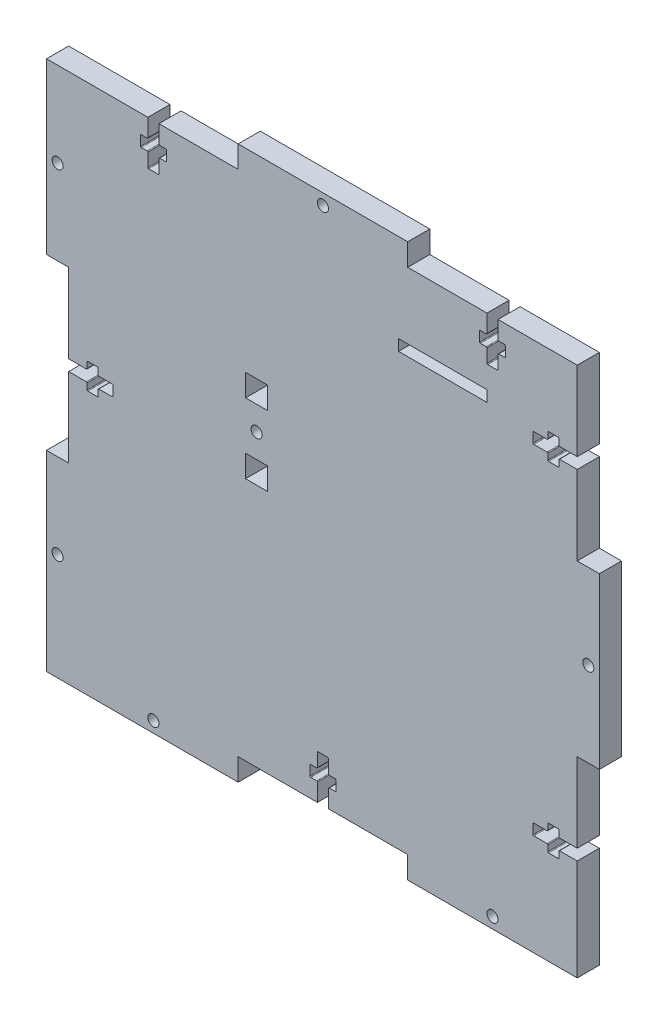
SolidWorks part; units mm, degrees
ref_plane "Front Plane" through (0, 0, 0) normal (0, 0, 1) x (1, 0, 0)
ref_plane "Top Plane" through (0, 0, 0) normal (0, 1, 0) x (1, 0, 0)
ref_plane "Right Plane" through (0, 0, 0) normal (1, 0, 0) x (0, 0, -1)
sketch "Sketch1" plane through (0, 0, 0) normal (0, 0, 1) x (1, 0, 0)
  line L0 (-69, 69) -> (-23, 69)
  line L5 (-75, -75) -> (75, -75) construction
  line L6 (-75, -75) -> (-75, 75) construction
  line L7 (-75, 75) -> (75, 75) construction
  line L8 (75, -75) -> (75, 75) construction
  line L9 (75, 23) -> (69, 23)
  line L10 (69, -23) -> (75, -23)
  line L11 (-69, -69) -> (69, -69) construction
  line L12 (-69, -69) -> (-69, 69) construction
  line L13 (-69, 69) -> (69, 69) construction
  line L14 (69, -69) -> (69, 69) construction
  line L15 (-69, -69) -> (69, 69) construction
  line L16 (69, -69) -> (69, -23)
  line L17 (-23, 69) -> (-23, 75)
  line L18 (-23, 75) -> (23, 75)
  line L19 (23, 75) -> (23, 69)
  line L20 (23, 69) -> (69, 69)
  line L21 (75, -23) -> (75, 23)
  line L22 (69, 23) -> (69, 69)
  line L23 (-75, 23) -> (-69, 23)
  line L24 (-69, 69) -> (-75, 69)
  line L25 (-75, 69) -> (-75, 23)
  line L26 (69, -69) -> (69, -75)
  line L27 (69, -75) -> (23, -75)
  line L28 (23, -75) -> (23, -69)
  line L29 (23, -69) -> (-23, -69)
  line L30 (-23, -69) -> (-23, -75)
  line L31 (-23, -75) -> (-69, -75)
  line L32 (-69, -75) -> (-69, -69) construction
  line L33 (-69, 23) -> (-69, -23)
  line L34 (-69, -23) -> (-75, -23)
  line L35 (-75, -23) -> (-75, -69)
  line L36 (-75, -69) -> (-69, -69) construction
  line L37 (-46, 69) -> (-46, -75) construction
  line L38 (-69, 69) -> (69, -69) construction
  line L39 (-75, -75) -> (-69, -75)
  line L40 (-75, -75) -> (-75, -69)
  point P0 (0, 0)
  point P6 (-7, -7)
  point P26 (0, -75)
  point P27 (-75, 0)
  dimension "D1" = 150
  dimension "D2" = 150
  dimension "D5" = 46
  dimension "D3" = 6
  dimension "D6" = 6
  dimension "D7" = 6
extrude "Box Side" add sketch "Sketch1" along normal blind 6
sketch "Sketch2" plane through (0, 0, 6) normal (0, 0, 1) x (1, 0, 0)
  line L0 (23, 72) -> (-23, 72) construction
  line L1 (23, 75) -> (23, 69) construction
  line L2 (-23, 69) -> (-23, 75) construction
  line L3 (-46, 69) -> (-46, -75) construction
  line L5 (0, 75) -> (0, 69) construction
  line L6 (-23, 75) -> (23, 75) construction
  line L7 (-69, 69) -> (69, 69) construction
  line L16 (-46, 69) -> (-46, -75) construction
  line L21 (0, -69) -> (0, 69) construction
  line L35 (-69, 69) -> (-23, 69) construction
  line L36 (-44.5, 69) -> (-44.5, 64.2)
  line L37 (-44.3, 64) -> (-42.7, 64)
  line L38 (-42.5, 63.8) -> (-42.5, 61.2)
  line L39 (-42.7, 61) -> (-44.3, 61)
  line L40 (-44.5, 60.8) -> (-44.5, 57.2)
  line L46 (-44.7, 57) -> (-47.3, 57)
  line L48 (-44.5, 69) -> (-47.5, 69)
  line L51 (-47.5, 60.8) -> (-47.5, 57.2)
  line L52 (-49.3, 61) -> (-47.7, 61)
  line L53 (-49.5, 63.8) -> (-49.5, 61.2)
  line L54 (-47.7, 64) -> (-49.3, 64)
  line L55 (-47.5, 69) -> (-47.5, 64.2)
  line L56 (47.5, 69) -> (47.5, 64.2)
  line L57 (47.7, 64) -> (49.3, 64)
  line L58 (49.5, 63.8) -> (49.5, 61.2)
  line L59 (49.3, 61) -> (47.7, 61)
  line L60 (47.5, 60.8) -> (47.5, 57.2)
  line L61 (44.5, 69) -> (47.5, 69)
  line L62 (44.7, 57) -> (47.3, 57)
  line L63 (44.5, 60.8) -> (44.5, 57.2)
  line L64 (42.7, 61) -> (44.3, 61)
  line L65 (42.5, 63.8) -> (42.5, 61.2)
  line L66 (44.3, 64) -> (42.7, 64)
  line L67 (44.5, 69) -> (44.5, 64.2)
  line L68 (-69, -69) -> (69, 69) construction
  line L69 (-69, -69) -> (69, 69) construction
  line L70 (75, 0) -> (69, 0) construction
  line L71 (72, 23) -> (72, -23) construction
  line L72 (69, 44.5) -> (64.2, 44.5)
  line L73 (64, 44.3) -> (64, 42.7)
  line L74 (63.8, 42.5) -> (61.2, 42.5)
  line L75 (61, 42.7) -> (61, 44.3)
  line L76 (60.8, 44.5) -> (57.2, 44.5)
  line L77 (57, 44.7) -> (57, 47.3)
  line L78 (69, 44.5) -> (69, 47.5)
  line L79 (60.8, 47.5) -> (57.2, 47.5)
  line L80 (61, 49.3) -> (61, 47.7)
  line L81 (63.8, 49.5) -> (61.2, 49.5)
  line L82 (64, 47.7) -> (64, 49.3)
  line L83 (69, 47.5) -> (64.2, 47.5)
  line L84 (69, -47.5) -> (64.2, -47.5)
  line L85 (64, -47.7) -> (64, -49.3)
  line L86 (63.8, -49.5) -> (61.2, -49.5)
  line L87 (61, -49.3) -> (61, -47.7)
  line L88 (60.8, -47.5) -> (57.2, -47.5)
  line L89 (69, -44.5) -> (69, -47.5)
  line L90 (57, -44.7) -> (57, -47.3)
  line L91 (60.8, -44.5) -> (57.2, -44.5)
  line L92 (61, -42.7) -> (61, -44.3)
  line L93 (63.8, -42.5) -> (61.2, -42.5)
  line L94 (64, -44.3) -> (64, -42.7)
  line L95 (69, -44.5) -> (64.2, -44.5)
  line L120 (-69, 69) -> (69, -69) construction
  line L121 (-69, 69) -> (69, -69) construction
  line L122 (-1.5, -69) -> (1.5, -69)
  line L123 (-23, -69) -> (23, -69) construction
  line L124 (1.5, -69) -> (1.5, -64.2)
  line L125 (1.7, -64) -> (3.3, -64)
  line L126 (3.5, -63.8) -> (3.5, -61.2)
  line L127 (3.3, -61) -> (1.7, -61)
  line L128 (1.5, -60.8) -> (1.5, -57.2)
  line L129 (1.3, -57) -> (-1.3, -57)
  line L130 (-1.5, -60.8) -> (-1.5, -57.2)
  line L131 (-3.3, -61) -> (-1.7, -61)
  line L132 (-3.5, -63.8) -> (-3.5, -61.2)
  line L133 (-1.7, -64) -> (-3.3, -64)
  line L134 (-1.5, -69) -> (-1.5, -64.2)
  line L135 (-69, -1.5) -> (-64.2, -1.5)
  line L136 (-64, -1.7) -> (-64, -3.3)
  line L137 (-63.8, -3.5) -> (-61.2, -3.5)
  line L138 (-61, -3.3) -> (-61, -1.7)
  line L139 (-60.8, -1.5) -> (-57.2, -1.5)
  line L140 (-57, 1.3) -> (-57, -1.3)
  line L141 (-60.8, 1.5) -> (-57.2, 1.5)
  line L142 (-61, 3.3) -> (-61, 1.7)
  line L143 (-63.8, 3.5) -> (-61.2, 3.5)
  line L144 (-64, 1.7) -> (-64, 3.3)
  line L145 (-69, 1.5) -> (-64.2, 1.5)
  line L146 (-69, -1.5) -> (-69, 1.5)
  line L147 (-69, -72) -> (-23, -72) construction
  line L148 (-23, 69) -> (-75, 69) construction
  line L149 (-23, -75) -> (-23, -69) construction
  line L150 (-69, -69) -> (-69, -75) construction
  line L151 (-75, -75) -> (-23, -75) construction
  circle A0 centre (0, 72) radius 1.5
  arc A1 (-44.5, 57.2) -> (-44.7, 57) centre (-44.7, 57.2) cw
  arc A2 (-44.3, 61) -> (-44.5, 60.8) centre (-44.3, 60.8) ccw
  arc A3 (-42.5, 61.2) -> (-42.7, 61) centre (-42.7, 61.2) cw
  arc A4 (-42.7, 64) -> (-42.5, 63.8) centre (-42.7, 63.8) cw
  arc A5 (-44.5, 64.2) -> (-44.3, 64) centre (-44.3, 64.2) ccw
  arc A6 (-47.5, 64.2) -> (-47.7, 64) centre (-47.7, 64.2) cw
  arc A7 (-49.3, 64) -> (-49.5, 63.8) centre (-49.3, 63.8) ccw
  arc A8 (-49.5, 61.2) -> (-49.3, 61) centre (-49.3, 61.2) ccw
  arc A9 (-47.7, 61) -> (-47.5, 60.8) centre (-47.7, 60.8) cw
  arc A10 (-47.5, 57.2) -> (-47.3, 57) centre (-47.3, 57.2) ccw
  arc A11 (47.5, 57.2) -> (47.3, 57) centre (47.3, 57.2) cw
  arc A12 (47.7, 61) -> (47.5, 60.8) centre (47.7, 60.8) ccw
  arc A13 (49.5, 61.2) -> (49.3, 61) centre (49.3, 61.2) cw
  arc A14 (49.3, 64) -> (49.5, 63.8) centre (49.3, 63.8) cw
  arc A15 (47.5, 64.2) -> (47.7, 64) centre (47.7, 64.2) ccw
  arc A16 (44.5, 64.2) -> (44.3, 64) centre (44.3, 64.2) cw
  arc A17 (42.7, 64) -> (42.5, 63.8) centre (42.7, 63.8) ccw
  arc A18 (42.5, 61.2) -> (42.7, 61) centre (42.7, 61.2) ccw
  arc A19 (44.3, 61) -> (44.5, 60.8) centre (44.3, 60.8) cw
  arc A20 (44.5, 57.2) -> (44.7, 57) centre (44.7, 57.2) ccw
  arc A21 (57.2, 44.5) -> (57, 44.7) centre (57.2, 44.7) cw
  arc A22 (61, 44.3) -> (60.8, 44.5) centre (60.8, 44.3) ccw
  arc A23 (61.2, 42.5) -> (61, 42.7) centre (61.2, 42.7) cw
  arc A24 (64, 42.7) -> (63.8, 42.5) centre (63.8, 42.7) cw
  arc A25 (64.2, 44.5) -> (64, 44.3) centre (64.2, 44.3) ccw
  arc A26 (64.2, 47.5) -> (64, 47.7) centre (64.2, 47.7) cw
  arc A27 (64, 49.3) -> (63.8, 49.5) centre (63.8, 49.3) ccw
  arc A28 (61.2, 49.5) -> (61, 49.3) centre (61.2, 49.3) ccw
  arc A29 (61, 47.7) -> (60.8, 47.5) centre (60.8, 47.7) cw
  arc A30 (57.2, 47.5) -> (57, 47.3) centre (57.2, 47.3) ccw
  arc A31 (57.2, -47.5) -> (57, -47.3) centre (57.2, -47.3) cw
  arc A32 (61, -47.7) -> (60.8, -47.5) centre (60.8, -47.7) ccw
  arc A33 (61.2, -49.5) -> (61, -49.3) centre (61.2, -49.3) cw
  arc A34 (64, -49.3) -> (63.8, -49.5) centre (63.8, -49.3) cw
  arc A35 (64.2, -47.5) -> (64, -47.7) centre (64.2, -47.7) ccw
  arc A36 (64.2, -44.5) -> (64, -44.3) centre (64.2, -44.3) cw
  arc A37 (64, -42.7) -> (63.8, -42.5) centre (63.8, -42.7) ccw
  arc A38 (61.2, -42.5) -> (61, -42.7) centre (61.2, -42.7) ccw
  arc A39 (61, -44.3) -> (60.8, -44.5) centre (60.8, -44.3) cw
  arc A40 (57.2, -44.5) -> (57, -44.7) centre (57.2, -44.7) ccw
  circle A41 centre (72, 0) radius 1.5
  arc A62 (1.5, -57.2) -> (1.3, -57) centre (1.3, -57.2) ccw
  arc A63 (1.7, -61) -> (1.5, -60.8) centre (1.7, -60.8) cw
  arc A64 (3.5, -61.2) -> (3.3, -61) centre (3.3, -61.2) ccw
  arc A65 (3.3, -64) -> (3.5, -63.8) centre (3.3, -63.8) ccw
  arc A66 (1.5, -64.2) -> (1.7, -64) centre (1.7, -64.2) cw
  arc A67 (-1.5, -64.2) -> (-1.7, -64) centre (-1.7, -64.2) ccw
  arc A68 (-3.3, -64) -> (-3.5, -63.8) centre (-3.3, -63.8) cw
  arc A69 (-3.5, -61.2) -> (-3.3, -61) centre (-3.3, -61.2) cw
  arc A70 (-1.7, -61) -> (-1.5, -60.8) centre (-1.7, -60.8) ccw
  arc A71 (-1.5, -57.2) -> (-1.3, -57) centre (-1.3, -57.2) cw
  arc A72 (-57.2, -1.5) -> (-57, -1.3) centre (-57.2, -1.3) ccw
  arc A73 (-61, -1.7) -> (-60.8, -1.5) centre (-60.8, -1.7) cw
  arc A74 (-61.2, -3.5) -> (-61, -3.3) centre (-61.2, -3.3) ccw
  arc A75 (-64, -3.3) -> (-63.8, -3.5) centre (-63.8, -3.3) ccw
  arc A76 (-64.2, -1.5) -> (-64, -1.7) centre (-64.2, -1.7) cw
  arc A77 (-64.2, 1.5) -> (-64, 1.7) centre (-64.2, 1.7) ccw
  arc A78 (-64, 3.3) -> (-63.8, 3.5) centre (-63.8, 3.3) cw
  arc A79 (-61.2, 3.5) -> (-61, 3.3) centre (-61.2, 3.3) cw
  arc A80 (-61, 1.7) -> (-60.8, 1.5) centre (-60.8, 1.7) ccw
  arc A81 (-57.2, 1.5) -> (-57, 1.3) centre (-57.2, 1.3) cw
  circle A82 centre (-46, -72) radius 1.5
  circle A83 centre (46, -72) radius 1.5
  circle A84 centre (-72, 46) radius 1.5
  circle A85 centre (-72, -46) radius 1.5
  point P6 (0, 72)
  point P38 (0, 0)
  point P56 (-46, 57)
  point P88 (46, 57)
  point P161 (57, 46)
  point P162 (57, -46)
  point P198 (0, -57)
  point P231 (-57, 0)
  point P234 (-42.5, 62.5)
  dimension "D1" = 3
  dimension "D2" = 0.2
  dimension "D8" = 0.2
  dimension "D14" = 3
  dimension "D4" = 3
  dimension "D7" = 1.5
  dimension "D10" = 3
  dimension "D12" = 1.5
  dimension "D9" = 12
  dimension "D11" = 5
  dimension "D13" = 7
  dimension "D3" = 12
  dimension "D5" = 7
  dimension "D6" = 5
extrude "Screw Cut-outs" cut sketch "Sketch2" against normal through all
sketch "Sketch3" plane through (0, 0, 6) normal (0, 0, 1) x (1, 0, 0)
  line L0 (69, 23) -> (69, 44.5) construction
  line L1 (44.5, 51) -> (20.5, 51)
  line L2 (44.5, 51) -> (44.5, 48)
  line L3 (44.5, 48) -> (20.5, 48)
  line L4 (20.5, 51) -> (20.5, 48)
  line L5 (44.5, 69) -> (23, 69) construction
  line L6 (75, -23) -> (75, 23) construction
  line L7 (-15, 22.32) -> (-21, 22.32)
  line L8 (-15, 22.32) -> (-15, 16.32)
  line L9 (-15, 16.32) -> (-21, 16.32)
  line L10 (-21, 22.32) -> (-21, 16.32)
  line L11 (-15, 3.32) -> (-21, 3.32)
  line L12 (-15, 3.32) -> (-15, -2.68)
  line L13 (-15, -2.68) -> (-21, -2.68)
  line L14 (-21, 3.32) -> (-21, -2.68)
  line L15 (-23, -69) -> (-1.5, -69) construction
  line L16 (-18, 3.32) -> (-18, 16.32) construction
  circle A0 centre (-18, 9.82) radius 1.5
  point P22 (-18, 16.32)
  point P23 (-18, 3.32)
  point P27 (-18, 9.82)
  dimension "D9" = 3
  dimension "D1" = 3
  dimension "D2" = 24.5
  dimension "D3" = 24
  dimension "D4" = 18
  dimension "D5" = 6
  dimension "D6" = 90
  dimension "D7" = 66.32
  dimension "D8" = 13
extrude "Grooves" cut sketch "Sketch3" against normal through all
equation "\"filletRadius\"=0.2"
equation "\"D8@Sketch2\"=\"filletRadius\""
equation "\"D2@Sketch2\"=\"filletRadius\""
equation "\"fingerWidth\"= 46"
equation "\"D5@Sketch1\"=\"fingerWidth\""
equation "\"wallThickness\"= 6"
equation "\"D3@Sketch1\" = \"wallThickness\""
equation "\"D6@Sketch1\" = \"wallThickness\""
equation "\"D7@Sketch1\" = \"wallThickness\""
equation "\"D1@Box Side\" = \"wallThickness\""
equation "\"M3\"= 3"
equation "\"D14@Sketch2\"=\"M3\""
equation "\"D1@Sketch2\"=\"M3\""
equation "\"D12@Sketch2\"=\"M3\"/2"
equation "\"nutThickness\"=3"
equation "\"D10@Sketch2\" = \"nutThickness\""
equation "\"boltLength\"= 12"
equation "\"D9@Sketch2\" = \"boltLength\""
equation "\"distanceToNut\"= 5"
equation "\"D11@Sketch2\" = \"distanceToNut\""
equation "\"D13@Sketch2\" = \"nutWidth\""
equation "\"D7@Sketch2\"=\"M3\"/2"
equation "\"D4@Sketch2\" = \"nutThickness\""
equation "\"D3@Sketch2\" = \"boltLength\""
equation "\"D5@Sketch2\" = \"nutWidth\""
equation "\"D6@Sketch2\" = \"distanceToNut\""
equation "\"sideLength\"=150"
equation "\"D1@Sketch1\"=\"sideLength\""
equation "\"D2@Sketch1\"=\"sideLength\""
equation "\"nutWidth\"=7"
